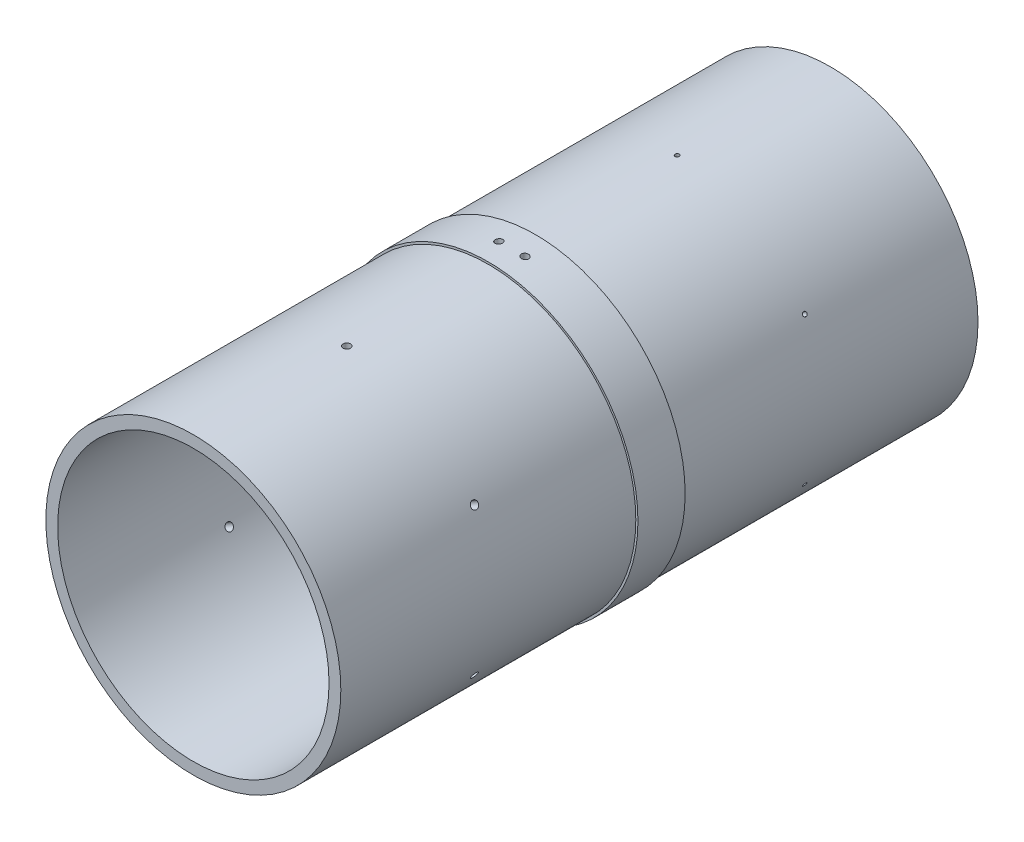
SolidWorks part; units mm, degrees
ref_plane "Front Plane" through (0, 0, 0) normal (0, 0, 1) x (1, 0, 0)
ref_plane "Top Plane" through (0, 0, 0) normal (0, 1, 0) x (1, 0, 0)
ref_plane "Right Plane" through (0, 0, 0) normal (1, 0, 0) x (0, 0, -1)
sketch "Sketch1" plane through (0, 0, 0) normal (0, 0, 1) x (1, 0, 0)
  circle A0 centre (0, 0) radius 79.375
  circle A1 centre (0, 0) radius 73.025
  dimension "D1" = 158.75
  dimension "D2" = 6.35
extrude "Boss-Extrude1" add sketch "Sketch1" along normal blind 342.9
ref_plane "Plane1" through (0, 0, 171.45) normal (0, 0, 1) x (1, 0, 0)
sketch "Sketch2" plane through (0, 0, 171.45) normal (0, 0, 1) x (1, 0, 0)
  circle A0 centre (0, 0) radius 79.375 construction
  circle A1 centre (0, 0) radius 79.375
  circle A2 centre (0, 0) radius 80.518
extrude "Boss-Extrude2" add sketch "Sketch2" against normal mid plane 25.4
sketch "Sketch5" plane through (0, 0, 171.45) normal (0, 0, 1) x (1, 0, 0)
  line L0 (0, 0) -> (0, 47.1719) construction
  line L1 (0, 0) -> (7.0176, 80.2116) construction
  circle A1 centre (0, 0) radius 80.518 construction
  dimension "D1" = 5
ref_plane "Plane2" through (7.0176, 80.2116, 0) normal (0.0872, 0.9962, 0) x (0, 0, 1)
hole_wizard "5/32 (0.15625) Diameter Hole1" positions "Sketch9" profile "Sketch10" hole size "5/32" standard "ANSI Inch" end condition up to next
sketch "Sketch9" plane through (7.0176, 80.2116, 0) normal (0.0872, 0.9962, 0) x (0, 0, 1)
  point P0 (171.45, 0)
sketch "Sketch10" plane through (7.0176, 80.2116, 171.45) normal (0, 0, 1) x (-0.9962, 0.0872, 0)
  line L0 (0, 0) -> (0, 7.493)
  line L1 (0, 7.493) -> (1.9844, 7.493)
  line L2 (1.9844, 7.493) -> (1.9844, 0)
  line L5 (1.9844, 0) -> (0, 0)
  line L11 (0, -6.35) -> (0, 107.95) construction
  dimension "Thru Hole Dia." = 3.9688
  dimension "Thru Hole Depth" = 7.493
mirror "Mirror1" about plane through (0, 0, 0) normal (1, 0, 0) of "5/32 (0.15625) Diameter Hole1"
ref_plane "Plane3" through (0, 79.375, 0) normal (0, 1, 0) x (1, 0, 0)
sketch "Sketch11" plane through (0, 79.375, 0) normal (0, 1, 0) x (1, 0, 0)
  line L0 (80.518, -158.75) -> (-80.518, -158.75) construction
  point P0 (0, -82.55)
  dimension "D1" = 76.2
hole_wizard "#4-40 Tapped Hole1" positions "Sketch12" profile "Sketch13" tap size "#4-40" standard "ANSI Inch" end condition up to next
sketch "Sketch12" plane through (0, 79.375, 0) normal (0, 1, 0) x (1, 0, 0)
  point P0 (0, -82.55)
sketch "Sketch13" plane through (0, 79.375, 82.55) normal (1, 0, 0) x (0, 0, 1)
  line L0 (0, 0) -> (0, 6.35)
  line L1 (0, 6.35) -> (1.1303, 6.35)
  line L2 (1.1303, 6.35) -> (1.1303, 0)
  line L5 (1.1303, 0) -> (0, 0)
  line L11 (0, -6.35) -> (0, 107.95) construction
  dimension "Thru Tap Drill Dia." = 2.2606
  dimension "Thru Tap Drill Depth" = 6.35
cosmetic thread "Hole Thread1" parameters "D2"=2.8448
pattern_circular "CirPattern1" count 6 over 360 about axis through (0, 0, 0) along (0, 0, 1) of "#4-40 Tapped Hole1"
cosmetic thread "Hole Thread2" parameters "D2"=2.8448
cosmetic thread "Hole Thread3" parameters "D2"=2.8448
cosmetic thread "Hole Thread4" parameters "D2"=2.8448
cosmetic thread "Hole Thread9" parameters "D2"=2.8448
cosmetic thread "Hole Thread10" parameters "D2"=2.8448
sketch "Sketch14" plane through (0, 79.375, 0) normal (0, 1, 0) x (1, 0, 0)
  line L0 (-79.375, -184.15) -> (79.375, -184.15) construction
  point P0 (0, -260.35)
  dimension "D1" = 76.2
hole_wizard "#10-32 Tapped Hole1" positions "Sketch15" profile "Sketch16" tap size "#10-32" standard "ANSI Inch" end condition up to next
sketch "Sketch15" plane through (0, 79.375, 0) normal (0, 1, 0) x (1, 0, 0)
  point P0 (0, -260.35)
sketch "Sketch16" plane through (0, 79.375, 260.35) normal (1, 0, 0) x (0, 0, 1)
  line L0 (0, 0) -> (0, 6.35)
  line L1 (0, 6.35) -> (2.0193, 6.35)
  line L2 (2.0193, 6.35) -> (2.0193, 0)
  line L5 (2.0193, 0) -> (0, 0)
  line L11 (0, -6.35) -> (0, 107.95) construction
  dimension "Thru Tap Drill Dia." = 4.0386
  dimension "Thru Tap Drill Depth" = 6.35
cosmetic thread "Hole Thread5" parameters "D2"=4.826
pattern_circular "CirPattern2" count 6 over 360 about axis through (0, 0, 342.9) along (0, 0, 1) of "#10-32 Tapped Hole1"
cosmetic thread "Hole Thread6" parameters "D2"=4.826
cosmetic thread "Hole Thread7" parameters "D2"=4.826
cosmetic thread "Hole Thread8" parameters "D2"=4.826
cosmetic thread "Hole Thread11" parameters "D2"=4.826
cosmetic thread "Hole Thread12" parameters "D2"=4.826
